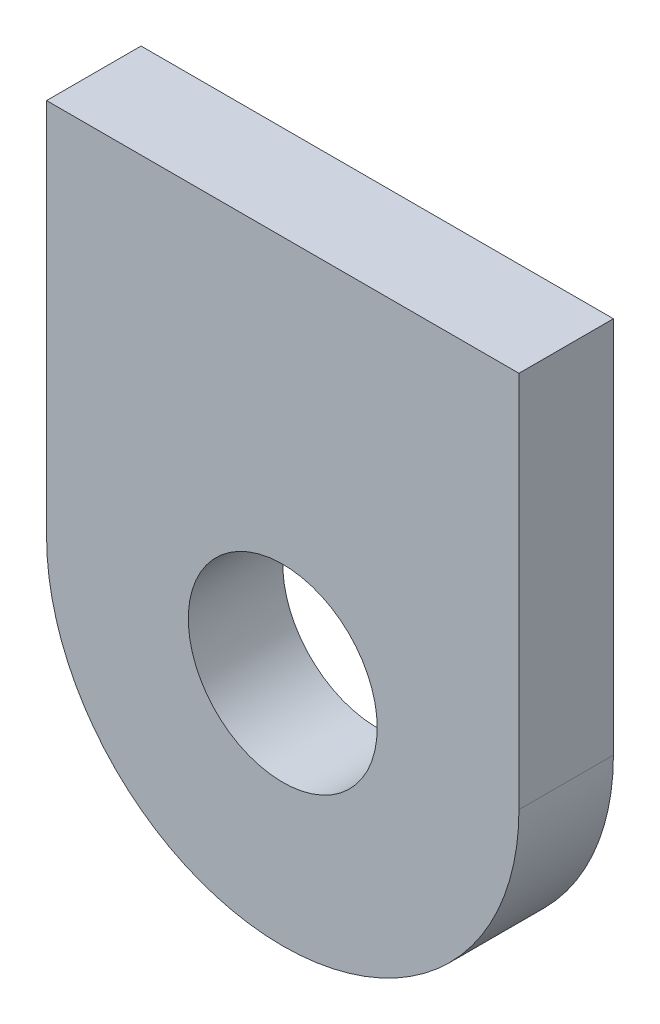
SolidWorks part; units mm, degrees
ref_plane "前视基准面" through (0, 0, 0) normal (0, 0, 1) x (1, 0, 0)
ref_plane "上视基准面" through (0, 0, 0) normal (0, 1, 0) x (1, 0, 0)
ref_plane "右视基准面" through (0, 0, 0) normal (1, 0, 0) x (0, 0, -1)
sketch "草图1" plane through (0, 0, 0) normal (0, 0, 1) x (1, 0, 0)
  line L0 (0, 0) -> (150, 0)
  line L1 (150, 0) -> (150, -120)
  line L2 (0, -120) -> (0, 0)
  arc A0 (150, -120) -> (0, -120) centre (75, -120) cw
  circle A1 centre (75, -120) radius 30
  dimension "D1" = 120
  dimension "D3" = 60
  dimension "D2" = 150
base flange "基体-法兰1" sketch "草图1" thickness 30 reverse thickness direction no parameters "D1"=1
sketch "折弯-线1" plane through (0, 0, 0) normal (0, 1, 0) x (1, 0, 0)
sketch "边界框1" plane through (0, 0, 0) normal (0, 1, 0) x (1, 0, 0)
sheet metal parameters "钣金6" thickness 30 parameters "D1"=1
flat pattern "平板型式6" [suppressed]
sketch "折弯-线2" plane through (0, 0, 0) normal (0, 1, 0) x (1, 0, 0)
sketch "边界框2" [suppressed] plane through (0, 0, 0) normal (0, 1, 0) x (1, 0, 0)
